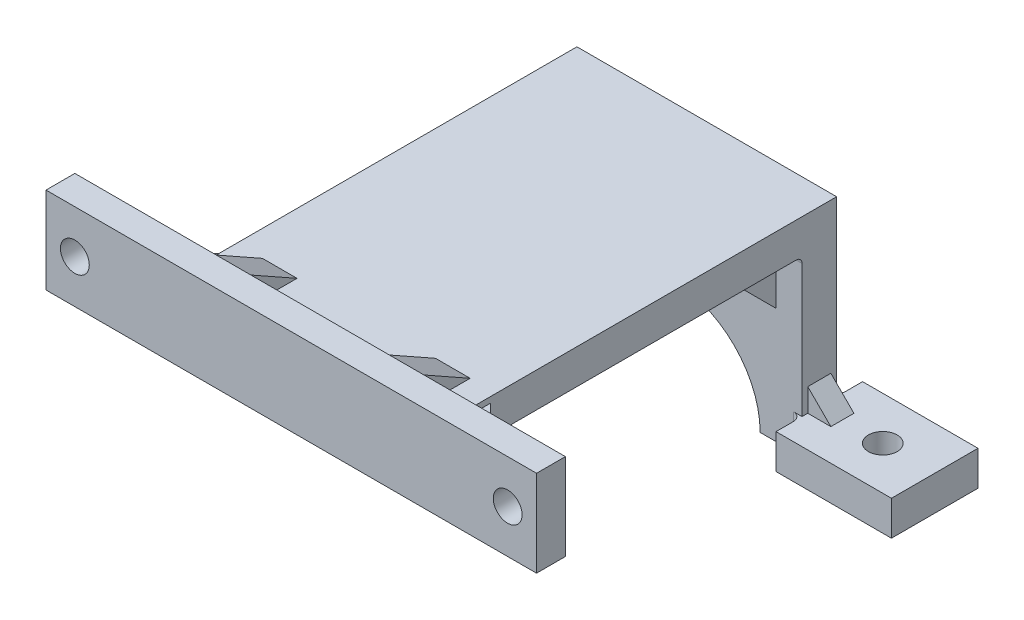
SolidWorks part; units mm, degrees
ref_plane "前视基准面" through (0, 0, 0) normal (0, 0, 1) x (1, 0, 0)
ref_plane "上视基准面" through (0, 0, 0) normal (0, 1, 0) x (1, 0, 0)
ref_plane "右视基准面" through (0, 0, 0) normal (1, 0, 0) x (0, 0, -1)
sketch "草图1" plane through (0, 0, 0) normal (0, 0, 1) x (1, 0, 0)
  line L1 (-42.5, 7.5) -> (42.5, 7.5)
  line L2 (-42.5, 7.5) -> (-42.5, -7.5)
  line L3 (-42.5, -7.5) -> (42.5, -7.5)
  line L4 (42.5, 7.5) -> (42.5, -7.5)
  line L5 (0, -7.5) -> (0, 7.5) construction
  line L6 (-42.5, 0) -> (42.5, 0) construction
  point P0 (0, 0)
  dimension "D1" = 15
  dimension "D2" = 85
extrude "凸台-拉伸1" add sketch "草图1" along normal blind 5
sketch "草图2" plane through (0, 0, 5) normal (0, 0, 1) x (1, 0, 0)
  circle A0 centre (-37.5, 0) radius 2.5
  circle A1 centre (37.5, 0) radius 2.5
  point P4 (0, 0)
  point P6 (0, 0)
  dimension "D3" = 5
  dimension "D4" = 5
  dimension "D1" = 37.5
  dimension "D2" = 37.5
extrude "切除-拉伸1" cut sketch "草图2" against normal blind 5
sketch "草图3" plane through (0, 0, 0) normal (0, 0, -1) x (-1, 0, 0)
  line L1 (-22.5, 3) -> (22.5, 3)
  line L2 (-22.5, 3) -> (-22.5, -3)
  line L3 (-22.5, -3) -> (22.5, -3)
  line L4 (22.5, 3) -> (22.5, -3)
  line L5 (0, -3) -> (0, 3) construction
  line L6 (-22.5, 0) -> (22.5, 0) construction
  point P0 (0, 0)
  dimension "D1" = 6
  dimension "D2" = 45
extrude "凸台-拉伸2" add sketch "草图3" along normal blind 67
sketch "草图4" plane through (0, -3, 0) normal (0, -1, 0) x (1, 0, 0)
  line L0 (-22.5, -67) -> (-22.5, 0) construction
  line L1 (-22.5, -67) -> (22.5, -67)
  line L2 (-22.5, -67) -> (-22.5, -61)
  line L3 (-22.5, -61) -> (22.5, -61)
  line L4 (22.5, -67) -> (22.5, -61)
  line L5 (22.5, -67) -> (-22.5, -67) construction
  line L6 (22.5, -67) -> (22.5, 0) construction
  dimension "D1" = 6
extrude "凸台-拉伸3" add sketch "草图4" along normal blind 30
sketch "草图7" plane through (0, -33, 0) normal (0, -1, 0) x (1, 0, 0)
  line L0 (22.5, -61) -> (-22.5, -61) construction
  line L1 (-22.5, -61) -> (-22.5, -67) construction
  line L2 (22.5, -56.5) -> (22.5, -71.5)
  line L3 (-42.5, -56.5) -> (-22.5, -56.5)
  line L4 (-42.5, -56.5) -> (-42.5, -71.5)
  line L5 (-42.5, -71.5) -> (-22.5, -71.5)
  line L6 (42.5, -56.5) -> (42.5, -71.5)
  line L7 (0, -71.5) -> (0, -56.5) construction
  line L8 (-42.5, -64) -> (-22.5, -64) construction
  line L9 (22.5, -61) -> (22.5, 0) construction
  line L10 (-22.5, -56.5) -> (-22.5, -71.5)
  line L11 (22.5, -56.5) -> (42.5, -56.5)
  line L12 (22.5, -64) -> (42.5, -64) construction
  line L13 (22.5, -71.5) -> (42.5, -71.5)
  point P0 (0, -61)
  point P1 (-22.5, -64)
  point P4 (0, -64)
  dimension "D1" = 15
  dimension "D2" = 85
  dimension "D3" = 42.5
extrude "凸台-拉伸4" add sketch "草图7" against normal blind 6
sketch "草图5" plane through (0, 0, -67) normal (0, 0, -1) x (-1, 0, 0)
  line L0 (22.5, -33) -> (-22.5, -33) construction
  line L1 (-15.25, -33) -> (15.25, -33)
  arc A0 (15.25, -33) -> (-15.25, -33) centre (0, -33) ccw
  dimension "D1" = 30.5
extrude "切除-拉伸3" cut sketch "草图5" against normal blind 6
ref_plane "基准面1" through (15, 0, 0) normal (1, 0, 0) x (0, 0, -1)
ref_plane "基准面2" through (-15, 0, 0) normal (1, 0, 0) x (0, 0, -1)
sketch "草图8" plane through (15, 0, 0) normal (1, 0, 0) x (0, 0, -1)
  line L0 (51, -3) -> (61, -13)
  line L1 (61, -3) -> (0, -3) construction
  line L2 (61, -27) -> (61, -3) construction
  line L3 (61, -13) -> (61, -3)
  line L4 (61, -3) -> (51, -3)
  dimension "D1" = 10
extrude "凸台-拉伸5" add sketch "草图8" along normal mid plane 6
sketch "草图10" plane through (-15, 0, 0) normal (1, 0, 0) x (0, 0, -1)
  line L3 (61, -3) -> (51, -3)
  line L4 (51, -3) -> (61, -13)
  line L5 (61, -13) -> (61, -3)
  line L6 (61, -3) -> (51, -3)
  line L7 (51, -3) -> (61, -13)
  line L8 (61, -13) -> (61, -3)
  dimension "D1" = 0
extrude "凸台-拉伸6" add sketch "草图10" along normal mid plane 6
fillet "圆角1" radius 1 3 edges at (0, -3, -61) (20.25, -3, -61) (-20.25, -3, -61)
sketch "草图11" plane through (0, -33, 0) normal (0, -1, 0) x (1, 0, 0)
  line L0 (0, 0) -> (0, -23.1579) construction
  line L1 (-42.5, -56.5) -> (-42.5, -71.5) construction
  circle A0 centre (-33.5, -64) radius 2.5
  circle A1 centre (33.5, -64) radius 2.5
  point P7 (-42.5, -64)
  dimension "D2" = 5
  dimension "D1" = 23.1579
  dimension "D3" = 9
extrude "切除-拉伸4" cut sketch "草图11" against normal blind 6
fillet "圆角2" radius 1.5 4 edges at (-22.5, -30, -61) (-22.5, -30, -67) (22.5, -30, -67) (22.5, -30, -61)
ref_plane "基准面3" through (0, 0, -64) normal (0, 0, -1) x (-1, 0, 0)
sketch "草图12" plane through (0, 0, -64) normal (0, 0, -1) x (-1, 0, 0)
  line L0 (-22.5, -23) -> (-26.5, -27)
  line L1 (-22.5, 3) -> (-22.5, -27) construction
  line L2 (-22.5, -27) -> (-42.5, -27) construction
  line L3 (-26.5, -27) -> (-22.5, -27)
  line L4 (-22.5, -27) -> (-22.5, -23)
  dimension "D1" = 4
extrude "凸台-拉伸7" add sketch "草图12" along normal mid plane 4
mirror "镜向1" about plane through (0, 0, 0) normal (1, 0, 0) of "凸台-拉伸7"
ref_plane "基准面4" through (0, 0, 0) normal (0, -1, 0) x (-1, 0, 0)
sketch "草图13" plane through (0, 0, 0) normal (0, -1, 0) x (-1, 0, 0)
  line L0 (-22.5, 7) -> (-29.5, 0)
  line L1 (-22.5, 60) -> (-22.5, 0) construction
  line L2 (42.5, 0) -> (-42.5, 0) construction
  line L3 (-29.5, 0) -> (-22.5, 0)
  line L4 (-22.5, 0) -> (-22.5, 7)
  dimension "D1" = 7
extrude "凸台-拉伸8" add sketch "草图13" along normal mid plane 4
mirror "镜向2" about plane through (0, 0, 0) normal (1, 0, 0) of "凸台-拉伸8"
sketch "草图14" plane through (15, 0, 0) normal (1, 0, 0) x (0, 0, -1)
  line L0 (0, 7.5) -> (8, 3)
  line L1 (67, 3) -> (0, 3) construction
  line L2 (8, 3) -> (0, 3)
  line L3 (0, 3) -> (0, 7.5)
  line L4 (0, 0) -> (-9.8898, 0) construction
  line L5 (-24.75, 0) -> (24.75, 0) construction
  line L6 (8, -3) -> (0, -3)
  line L7 (0, -7.5) -> (8, -3)
  line L8 (0, -3) -> (0, -7.5)
  dimension "D1" = 8
extrude "凸台-拉伸9" add sketch "草图14" along normal mid plane 6
sketch "草图15" plane through (-15, 0, 0) normal (1, 0, 0) x (0, 0, -1)
  line L0 (0, -7.5) -> (8, -3) construction
  line L1 (8, -3) -> (0, -3) construction
  line L2 (0, -3) -> (0, -7.5) construction
  line L3 (0, 7.5) -> (0, 3) construction
  line L4 (0, 3) -> (8, 3) construction
  line L5 (8, 3) -> (0, 7.5) construction
  line L6 (0, -7.5) -> (8, -3)
  line L7 (8, -3) -> (0, -3)
  line L8 (0, -3) -> (0, -7.5)
  line L9 (0, 7.5) -> (0, 3)
  line L10 (0, 3) -> (8, 3)
  line L11 (8, 3) -> (0, 7.5)
extrude "凸台-拉伸10" add sketch "草图15" along normal mid plane 6
